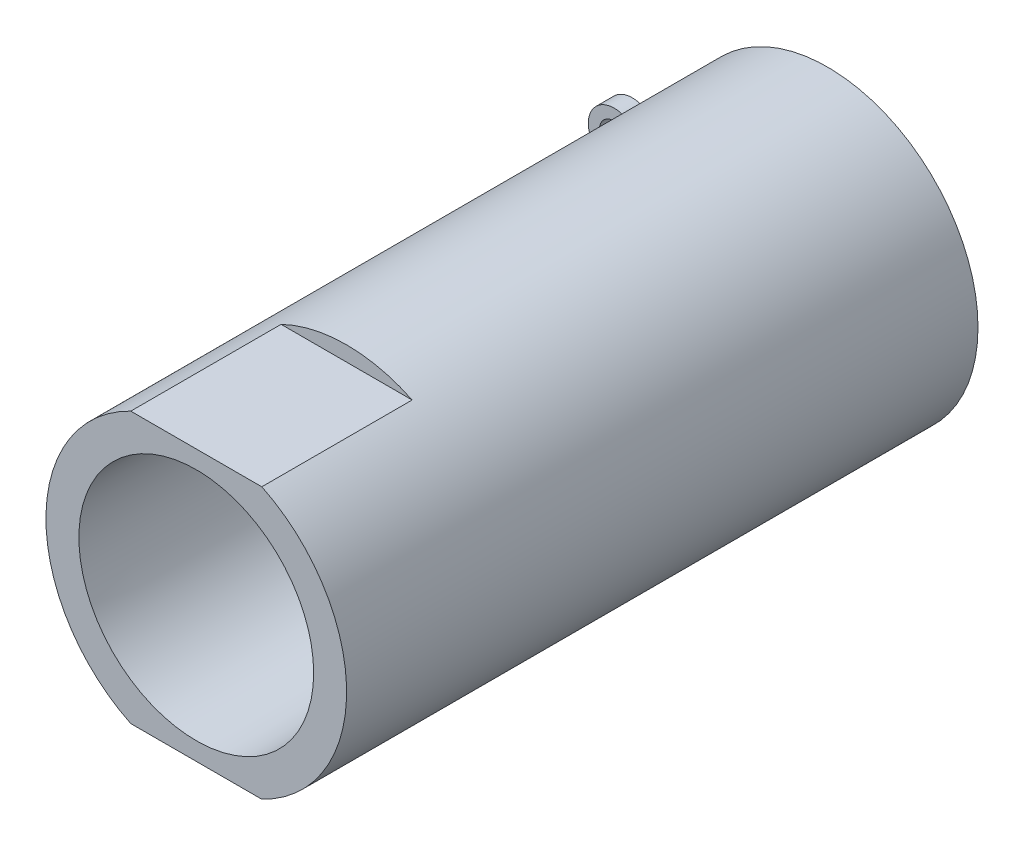
SolidWorks part; units mm, degrees
ref_plane "Front Plane" through (0, 0, 0) normal (0, 0, 1) x (1, 0, 0)
ref_plane "Top Plane" through (0, 0, 0) normal (0, 1, 0) x (1, 0, 0)
ref_plane "Right Plane" through (0, 0, 0) normal (1, 0, 0) x (0, 0, -1)
sketch "Sketch1" plane through (0, 0, 0) normal (0, 0, 1) x (1, 0, 0)
  circle A0 centre (0, 0) radius 10
  dimension "D1" = 20
extrude "Boss-Extrude1" add sketch "Sketch1" along normal blind 42
sketch "Sketch2" plane through (0, 0, 42) normal (0, 0, 1) x (1, 0, 0)
  circle A0 centre (0, 0) radius 5.25
  dimension "D1" = 10.5
extrude "Cut-Extrude1" cut sketch "Sketch2" against normal up to next
sketch "Sketch3" plane through (0, 0, 42) normal (0, 0, 1) x (1, 0, 0)
  circle A0 centre (0, 0) radius 7.25
  dimension "D1" = 14.5
extrude "Cut-Extrude2" cut sketch "Sketch3" against normal offset from surface (32 mm away) 10 up to face at (5.25, 0, 0)
sketch "Sketch4" plane through (0, 0, 0) normal (0, 0, -1) x (-1, 0, 0)
  line L0 (9.9801, -0.6299) -> (11.3722, -0.6299)
  line L1 (9.9801, 0.6308) -> (11.3721, 0.6308)
  arc A0 (9.9801, 0.6308) -> (9.9801, -0.6299) centre (0, 0) ccw
  arc A1 (11.3721, 0.6308) -> (11.3722, -0.6299) centre (12.9878, 0.0005) cw
  circle A2 centre (0, 0) radius 10 construction
  circle A3 centre (12.9878, 0.0005) radius 1
  circle A4 centre (0, 0) radius 10 construction
  circle A7 centre (0, 0) radius 5.25
  circle A8 centre (0, 0) radius 5.25
  point P7 (10, 0)
  dimension "D1" = 0
extrude "Boss-Extrude2" add sketch "Sketch4" against normal blind 1.2
sketch "Sketch5" plane through (0, 0, 42) normal (0, 0, 1) x (1, 0, 0)
  line L0 (-4.3589, 9) -> (4.3589, 9)
  line L1 (10, 0) -> (-10, 0) construction
  line L2 (-4.3589, -9) -> (4.3589, -9)
  circle A0 centre (0, 0) radius 10 construction
  arc A1 (4.3589, -9) -> (-4.3589, -9) centre (0, 0) cw
  arc A2 (-4.3589, 9) -> (4.3589, 9) centre (0, 0) cw
  circle M4 centre (0, 0) radius 10
  dimension "D1" = 9
extrude "Cut-Extrude3" cut sketch "Sketch5" against normal blind 10 contours L0 M4 | L2 M4 region at (0, 9.4018, 42) region at (0, -9.4018, 42)
draft "Draft1" type of draft neutral plane draft angle 1 faces to draft 1 face at (7.25, 0, 10) neutral plane through (0, 0, 10) neutral plane normal (0, 0, 1) parameters "D1"=1
chamfer "Chamfer1" distance 3 angle 45 1 edges at (7.25, 0, 10) first distance on face at (7.25, 0, 10)
